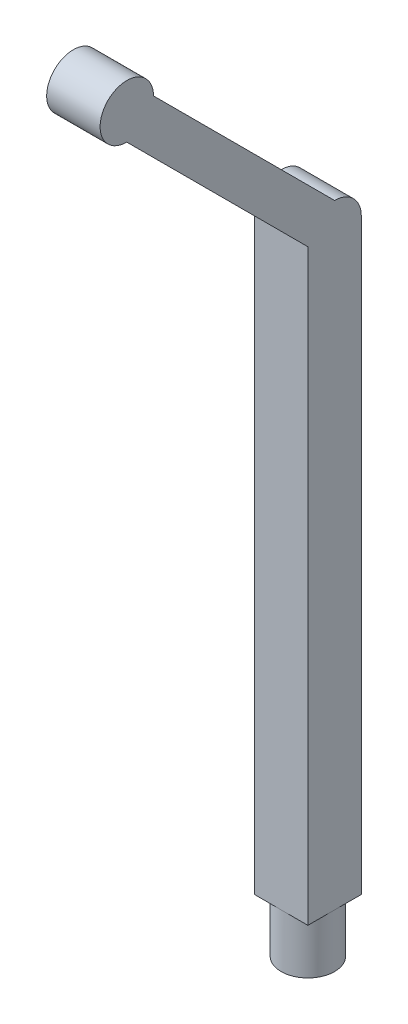
SolidWorks part; units mm, degrees
ref_plane "前视基准面" through (0, 0, 0) normal (0, 0, 1) x (1, 0, 0)
ref_plane "上视基准面" through (0, 0, 0) normal (0, 1, 0) x (1, 0, 0)
ref_plane "右视基准面" through (0, 0, 0) normal (1, 0, 0) x (0, 0, -1)
other "质心 (COM)"
sketch "草图1" plane through (0, 0, 0) normal (1, 0, 0) x (0, 0, -1)
  line L0 (5, 55) -> (-33.8909, 93.8909)
  line L1 (-5, 55) -> (5, 55)
  line L2 (-5, 55) -> (-5, -55)
  line L3 (-5, -55) -> (5, -55)
  line L4 (5, 55) -> (5, -55)
  line L5 (-5, 55) -> (5, -55) construction
  line L6 (-5, -55) -> (5, 55) construction
  line L7 (-33.8909, 93.8909) -> (-43.8909, 93.8909)
  line L8 (-43.8909, 93.8909) -> (-5, 55)
  circle A2 centre (-38.8909, 93.8909) radius 5
  circle A3 centre (0, -55) radius 5
  circle A4 centre (0, 55) radius 5
  point P0 (0, 0)
extrude "凸台-拉伸2" add sketch "草图1" along normal blind 10 contours A4 L0 A2 L8 | L1 A4 | L0 A4 L1 | L0 A4 | A4 L2 A3 L4 | L3 A3 | A2 region at (0, 56.9449, 0.6483) region at (0, 52.8779, 0) region at (0, 0, 0) region at (0, 57.9199, -2.9199) region at (0, 74.4454, 19.4454) region at (0, -52.8779, 0)
sketch "草图3" plane through (0, -55, 0) normal (0, -1, 0) x (1, 0, 0)
  circle A0 centre (5, 0) radius 5
extrude "凸台-拉伸3" add sketch "草图3" along normal blind 10
sketch "草图4" plane through (10, 0, 0) normal (1, 0, 0) x (0, 0, -1)
  point P0 (0, 55)
  point P1 (-38.8909, 93.8909)
